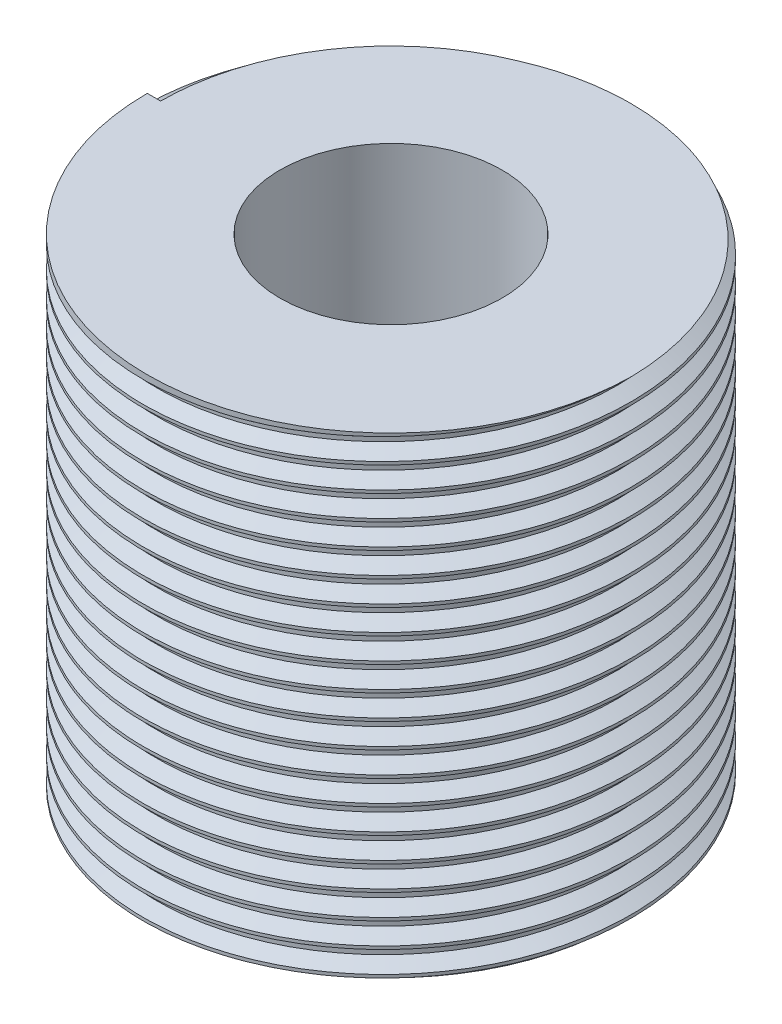
SolidWorks part; units mm, degrees
ref_plane "Front Plane" through (0, 0, 0) normal (0, 0, 1) x (1, 0, 0)
ref_plane "Top Plane" through (0, 0, 0) normal (0, 1, 0) x (1, 0, 0)
ref_plane "Right Plane" through (0, 0, 0) normal (1, 0, 0) x (0, 0, -1)
sketch "Sketch1" plane through (0, 0, 0) normal (0, 1, 0) x (1, 0, 0)
  circle A0 centre (0, 0) radius 19.75
  dimension "D1" = 39.5
extrude "Boss-Extrude1" add sketch "Sketch1" along normal blind 40
thread "Thread1" pitch 2 method cut profile "Thread Profile1" start angle 0, offset 0, length 40, pitch 2, diameter 39.5
ref_plane "Plane1" through (-19.75, 40, 0) normal (0, 0, 1) x (-1, 0, 0)
sketch "Thread Profile1" plane through (-19.75, 40, 0) normal (0, 0, 1) x (-1, 0, 0)
  line L0 (0, 0) -> (0, 2) construction
  line L11 (0, 0) -> (0, 1.75)
  line L12 (0, 1.75) -> (-1.0825, 1.125)
  line L13 (-1.0825, 1.125) -> (-1.0825, 0.625)
  line L15 (-1.0825, 0.625) -> (0, 0)
  line L17 (-1.0825, 0.875) -> (0, 0.875) construction
  point P2 (0, 0)
  dimension "Pitch" = 2
  dimension "Profile_Angle" = 60
  dimension "Profile_Land" = 0.5
  dimension "Profile_Height" = 1.0825
sketch "Sketch4" plane through (0, 40, 0) normal (0, 1, 0) x (1, 0, 0)
  circle A1 centre (0, 0) radius 9
extrude "Cut-Extrude1" cut sketch "Sketch4" against normal through all both and the other way through all
sketch "Sketch5" plane through (0, 0, 0) normal (0, 0, 1) x (1, 0, 0)
  line L1 (-25.8707, 44.718) -> (26.4896, 44.718)
  line L2 (-25.8707, 44.718) -> (-25.8707, 38.9963)
  line L3 (-25.8707, 38.9963) -> (26.4896, 38.9963)
  line L4 (26.4896, 44.718) -> (26.4896, 38.9963)
extrude "Cut-Extrude2" cut sketch "Sketch5" against normal through all both and the other way through all
